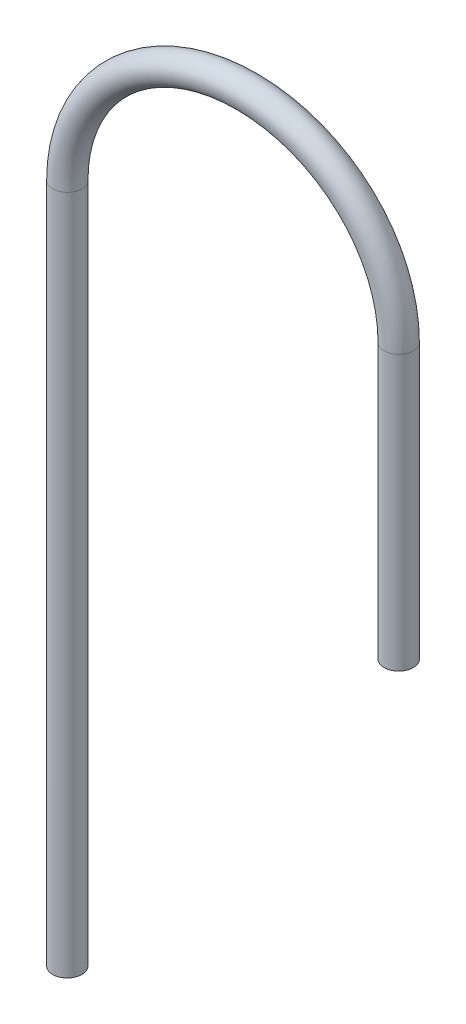
SolidWorks part; units mm, degrees
material "PE faible/moyenne densité"
ref_plane "Front" through (0, 0, 0) normal (0, 0, 1) x (1, 0, 0)
ref_plane "Top" through (0, 0, 0) normal (0, 1, 0) x (1, 0, 0)
ref_plane "Right" through (0, 0, 0) normal (1, 0, 0) x (0, 0, -1)
sketch3d "Esquisse3D1"
  line L0 (-14, 165, -59.25) -> (-14, 221.325, -59.25)
  line L1 (-76.8149, 221.325, -54.0281) -> (-76.8149, 81.65, -54.0281)
  arc A0 (-14, 221.325, -59.25) -> (-76.8149, 221.325, -54.0281) centre (-45.4075, 221.325, -56.6391) ccw
  circle A1 centre (-76.8149, 89.65, -54.0281) radius 1.1 construction
  point P3 (-42.7965, 221.325, -25.2316)
  point P10 (-76.8149, 88.55, -54.0281)
  dimension "D5" = 139.675
  dimension "D4" = 31.5158
  dimension "D1" = 165
  dimension "D2" = 59.25
  dimension "D3" = 14
  dimension "D6" = 81.65
sweep "Balayage-Mince1" add path "Esquisse3D1" circular profile diameter 6 parameters "D1"=1, "D3"=6
equation "\"D5@Esquisse3D1\"=140-((\"D6@Esquisse3D1\"-81)/2)"
